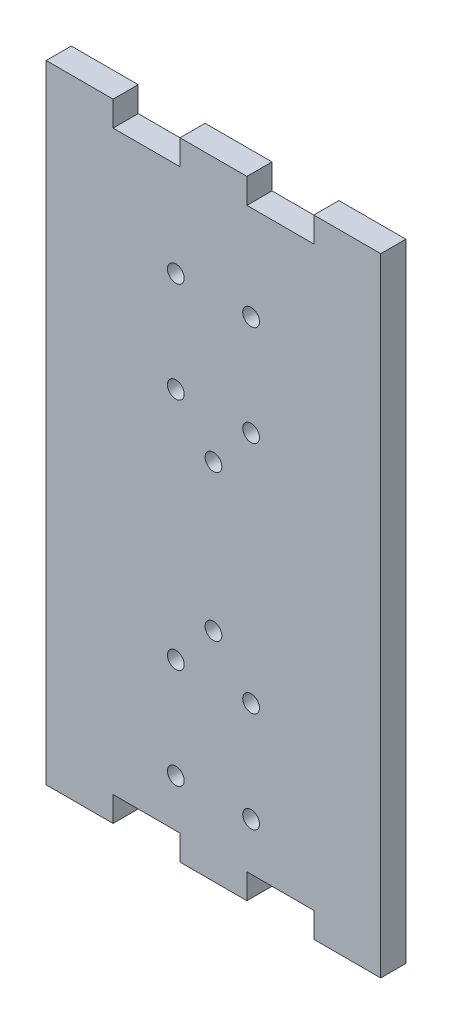
SolidWorks part; units mm, degrees
ref_plane "Front Plane" through (0, 0, 0) normal (0, 0, 1) x (1, 0, 0)
ref_plane "Top Plane" through (0, 0, 0) normal (0, 1, 0) x (1, 0, 0)
ref_plane "Right Plane" through (0, 0, 0) normal (1, 0, 0) x (0, 0, -1)
sketch "Sketch1" plane through (0, 0, 0) normal (0, 0, 1) x (1, 0, 0)
  line L0 (-1739.7044, 0) -> (85245.5138, 0) construction
  line L1 (0, -1739.7044) -> (0, 85245.5138) construction
  line L2 (-24, 69) -> (-8, 69)
  line L5 (-8, 75) -> (8, 75)
  line L7 (-24, 75) -> (-24, 69)
  line L8 (-8, 75) -> (-8, 69)
  line L9 (8, 75) -> (8, 69)
  line L10 (24, 75) -> (24, 69)
  line L22 (8, -69) -> (24, -69)
  line L23 (-24, 75) -> (-40, 75)
  line L24 (-40, 75) -> (-40, -75)
  line L25 (24, 75) -> (40, 75)
  line L26 (40, 75) -> (40, -75)
  line L27 (8, 69) -> (24, 69)
  line L28 (24, -75) -> (40, -75)
  line L29 (-24, -75) -> (-40, -75)
  line L30 (24, -75) -> (24, -69)
  line L31 (8, -75) -> (8, -69)
  line L32 (-8, -75) -> (-8, -69)
  line L33 (-24, -75) -> (-24, -69)
  line L34 (-8, -75) -> (8, -75)
  line L35 (-24, -69) -> (-8, -69)
  point P17 (-40, 0)
  point P23 (0, 75)
  dimension "D1" = 150
  dimension "D2" = 80
  dimension "D3" = 6
  dimension "D4" = 40
  dimension "D7" = 16
  dimension "D5" = 4
extrude "Boss-Extrude1" add sketch "Sketch1" along normal blind 6
sketch "Sketch2" plane through (0, 0, 6) normal (0, 0, 1) x (1, 0, 0)
  line L0 (0, -1000) -> (0, 49000) construction
  line L1 (-40, 75) -> (-40, -75) construction
  line L3 (24, 69) -> (8, 69) construction
  line L6 (-896.0655, -5.6183) -> (49103.9345, -5.6183) construction
  line L7 (-8, 69) -> (-24, 69) construction
  circle A8 centre (9, 46.3817) radius 2
  circle A9 centre (9, 22.3817) radius 2
  circle A10 centre (-9, 22.3817) radius 2
  circle A11 centre (-9, 46.3817) radius 2
  circle A12 centre (-9, -57.6183) radius 2
  circle A13 centre (-9, -33.6183) radius 2
  circle A14 centre (9, -33.6183) radius 2
  circle A15 centre (9, -57.6183) radius 2
  dimension "D2" = 4
  dimension "D5" = 4
  dimension "D6" = 9
  dimension "D1" = 40
  dimension "D3" = 9
  dimension "D4" = 22.6183
  dimension "D7" = 24
  dimension "D8" = 74.6183
extrude "Cut-Extrude1" cut sketch "Sketch2" against normal up to next
sketch "Sketch3" plane through (0, 0, 6) normal (0, 0, 1) x (1, 0, 0)
  line L0 (40, -75) -> (40, 75) construction
  line L1 (24, 69) -> (8, 69) construction
  line L2 (-896.2655, -5.6183) -> (49103.7345, -5.6183) construction
  line L3 (-24, 75) -> (-40, 75) construction
  circle A2 centre (0, 11.8817) radius 2
  circle A3 centre (0, -23.1183) radius 2
  dimension "D1" = 4
  dimension "D2" = 40
  dimension "D3" = 57.1183
  dimension "D4" = 80.6183
extrude "Cut-Extrude2" cut sketch "Sketch3" against normal up to next
